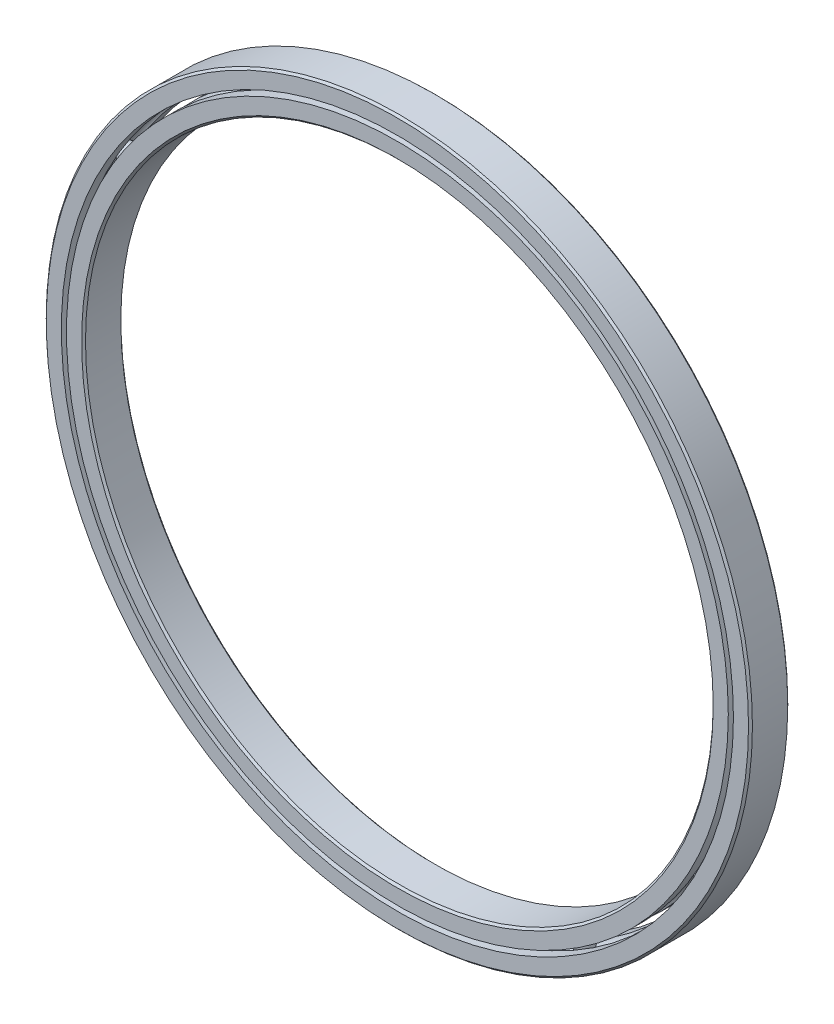
SolidWorks part; units mm, degrees
ref_plane "Front Plane" through (0, 0, 0) normal (0, 0, 1) x (1, 0, 0)
ref_plane "Top Plane" through (0, 0, 0) normal (0, 1, 0) x (1, 0, 0)
ref_plane "Right Plane" through (0, 0, 0) normal (1, 0, 0) x (0, 0, -1)
sketch "Sketch1" plane through (0, 0, 0) normal (1, 0, 0) x (0, 0, -1)
  line L0 (-3.175, 0) -> (3.175, 0) construction
  line L1 (0, 57.15) -> (0, -57.15) construction
  line L2 (2.8575, 57.15) -> (-2.8575, 57.15)
  line L3 (-2.8575, 57.15) -> (-3.175, 56.8325)
  line L4 (-3.175, 56.8325) -> (-3.175, 54.3902)
  line L5 (-3.175, 54.3902) -> (-1.4111, 54.3902)
  line L6 (3.175, 54.3902) -> (1.4111, 54.3902)
  line L7 (3.175, 56.8325) -> (3.175, 54.3902)
  line L8 (2.8575, 57.15) -> (3.175, 56.8325)
  line L9 (0, 57.15) -> (0, 53.975) construction
  line L10 (0, 53.975) -> (0, 50.8) construction
  arc A0 (-1.4111, 54.3902) -> (1.4111, 54.3902) centre (0, 53.975) cw
  point P14 (0, 50.8)
  dimension "Width" = 6.35
  dimension "OD" = 114.3
  dimension "D1" = 45
  dimension "D2" = 0.3175
  dimension "Shaft Dia" = 101.6
  dimension "D3" = 2.8222
  dimension "D4" = 0.4152
revolve "Revolve1" add sketch "Sketch1" angle 360 about L0
sketch "Sketch3" plane through (0, 0, 0) normal (1, 0, 0) x (0, 0, -1)
  line L0 (-3.175, 53.5598) -> (-1.4111, 53.5598)
  line L1 (0, 57.15) -> (0, -57.15) construction
  line L2 (-3.175, 56.8325) -> (-3.175, 54.3902) construction
  line L3 (-3.175, 53.5598) -> (-3.175, 51.1175)
  line L4 (-2.8575, 57.15) -> (-3.175, 56.8325) construction
  line L5 (-3.175, 51.1175) -> (-2.8575, 50.8)
  line L6 (-2.8575, 50.8) -> (2.8575, 50.8)
  line L7 (2.8575, 57.15) -> (2.8575, -57.15) construction
  line L8 (2.8575, 50.8) -> (3.175, 51.1175)
  line L9 (3.175, -56.8325) -> (3.175, 56.8325) construction
  line L10 (3.175, 51.1175) -> (3.175, 53.5598)
  line L11 (3.175, 53.5598) -> (1.4111, 53.5598)
  line L13 (2.8575, 57.15) -> (3.175, 56.8325) construction
  arc A0 (1.4111, 54.3902) -> (-1.4111, 54.3902) centre (0, 53.975) ccw construction
  arc A1 (1.4111, 53.5598) -> (-1.4111, 53.5598) centre (0, 53.975) cw
revolve "Revolve3" add sketch "Sketch3" angle 360 about L0
sketch "Sketch4" plane through (0, 0, 0) normal (1, 0, 0) x (0, 0, -1)
  line L0 (-1.4709, 53.975) -> (1.4709, 53.975)
  arc A2 (-1.4709, 53.975) -> (1.4709, 53.975) centre (0, 53.975) cw
  arc A3 (1.4111, 54.3902) -> (-1.4111, 54.3902) centre (0, 53.975) ccw construction
revolve "Revolve4" add sketch "Sketch4" angle 360 about L0
ref_axis "Axis1" through (0, 0, -3.175) along (0, 0, 1)
pattern_circular "CirPattern1" count 12 every 30 about axis through (0, 0, -3.175) along (0, 0, 1) of bodies 104
equation "\"D2@Sketch1\" = \"Width@Sketch1\"*.05"
equation "\"D3@Sketch1\" = \"Width@Sketch1\"/2.25"
equation "\"D4@Sketch1\" = (((\"OD@Sketch1\"-\"Width@Sketch1\")/2)/3.25)*.025"
equation "\"D2@CirPattern1\" = 360/\"Balls@CirPattern1\""
